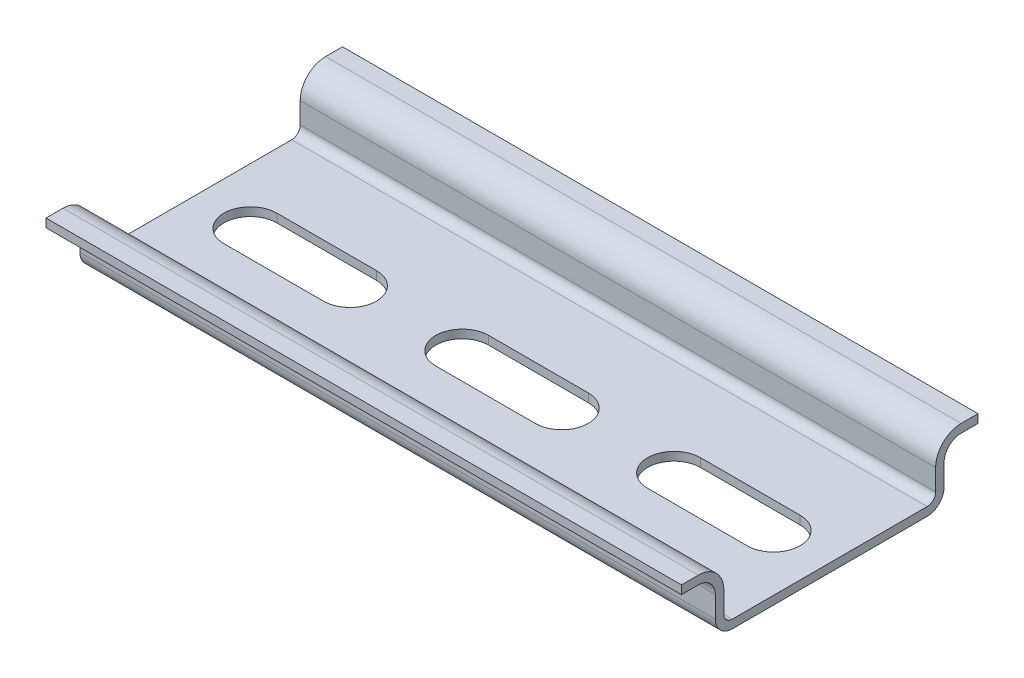
SolidWorks part; units mm, degrees
ref_plane "Front Plane" through (0, 0, 0) normal (0, 0, 1) x (1, 0, 0)
ref_plane "Top Plane" through (0, 0, 0) normal (0, 1, 0) x (1, 0, 0)
ref_plane "Right Plane" through (0, 0, 0) normal (1, 0, 0) x (0, 0, -1)
sketch "Sketch1" plane through (0, 0, 0) normal (1, 0, 0) x (0, 0, -1)
  line L0 (0, 0) -> (0, 18.2344) construction
  line L1 (0, 0) -> (26.621, 0) construction
  line L2 (-11.5, 0) -> (11.5, 0)
  line L3 (13.5, 2) -> (13.5, 4.5)
  line L4 (15.5, 6.5) -> (17.5, 6.5)
  line L5 (-13.5, 2) -> (-13.5, 4.5)
  line L6 (-15.5, 6.5) -> (-17.5, 6.5)
  arc A0 (13.5, 2) -> (11.5, 0) centre (11.5, 2) cw
  arc A1 (15.5, 6.5) -> (13.5, 4.5) centre (15.5, 4.5) ccw
  arc A2 (-13.5, 2) -> (-11.5, 0) centre (-11.5, 2) ccw
  arc A3 (-15.5, 6.5) -> (-13.5, 4.5) centre (-15.5, 4.5) cw
  point P9 (13.5, 0)
  dimension "D1" = 2
  dimension "D3" = 2
  dimension "D2" = 6.5
  dimension "D4" = 35
  dimension "D5" = 27
extrude "Extrude-Thin1" add sketch "Sketch1" along normal blind 37.5 and the other way blind 37.5 thin thin type one direction wall 1
sketch "Sketch2" plane through (0, 0, 0) normal (0, -1, 0) x (1, 0, 0)
  line L0 (0, 6.6969) -> (0, 0) construction
  line L1 (0, 0) -> (9.9599, 0) construction
  line L2 (-5.875, 3.125) -> (5.875, 3.125)
  line L3 (-5.875, -3.125) -> (5.875, -3.125)
  arc A0 (5.875, 3.125) -> (5.875, -3.125) centre (5.875, 0) cw
  arc A1 (-5.875, 3.125) -> (-5.875, -3.125) centre (-5.875, 0) ccw
  point P6 (0, 3.125)
  point P12 (0, -3.125)
  dimension "D2" = 11.75
  dimension "D1" = 6.25
extrude "Cut-Extrude1" cut sketch "Sketch2" against normal up to next
pattern_linear "LPattern1" count 2 spacing 25 along (1, 0, 0) count 2 spacing 25 along (-1, 0, 0) of "Cut-Extrude1"
